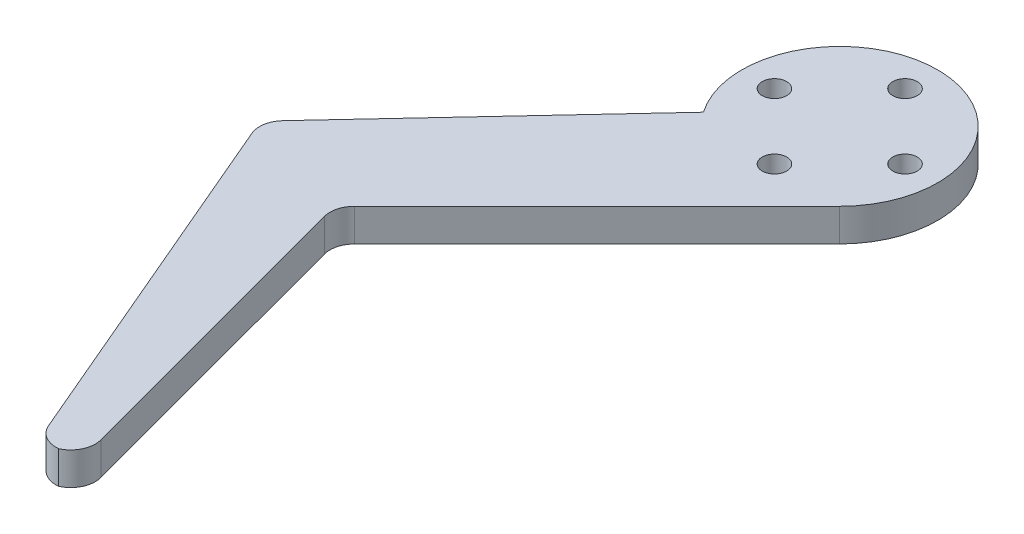
SolidWorks part; units mm, degrees
ref_plane "Plan de face" through (0, 0, 0) normal (0, 0, 1) x (1, 0, 0)
ref_plane "Plan de dessus" through (0, 0, 0) normal (0, 1, 0) x (1, 0, 0)
ref_plane "Plan de droite" through (0, 0, 0) normal (1, 0, 0) x (0, 0, -1)
sketch "Esquisse1" plane through (0, 0, 0) normal (0, 1, 0) x (1, 0, 0)
  line L0 (0, 19.3771) -> (0, -21.9875) construction
  line L2 (-27.2045, 0) -> (29.8145, 0) construction
  line L3 (0, 0) -> (8.4853, -8.4853) construction
  line L4 (8.4853, -8.4853) -> (0, -16.9706)
  line L5 (0, -16.9706) -> (-22.4643, -39.4349)
  line L6 (-22.4643, -39.4349) -> (-11.2188, -81.4525)
  line L7 (-11.2188, -81.4525) -> (-15.68, -82.6465)
  line L8 (-15.68, -82.6465) -> (-36.0477, -34.9435)
  line L9 (-36.0477, -34.9435) -> (-9.8516, -6.8517)
  arc A0 (8.4853, -8.4853) -> (-9.8516, -6.8517) centre (0, 0) ccw
  circle A1 centre (0, 8) radius 1.5
  circle A2 centre (8, 0) radius 1.5
  circle A3 centre (0, -8) radius 1.5
  circle A4 centre (-8, 0) radius 1.5
  dimension "D1" = 24
  dimension "D2" = 3
  dimension "D3" = 3
  dimension "D4" = 3
  dimension "D5" = 3
  dimension "D6" = 8
  dimension "D7" = 8
  dimension "D8" = 8
  dimension "D9" = 8
extrude "Boss.-Extru.1" add sketch "Esquisse1" along normal blind 4
fillet "Congé1" radius 3 4 edges at (-36.0477, 2, 34.9435) (-15.68, 2, 82.6465) (-11.2188, 2, 81.4525) (-22.4643, 2, 39.4349)
